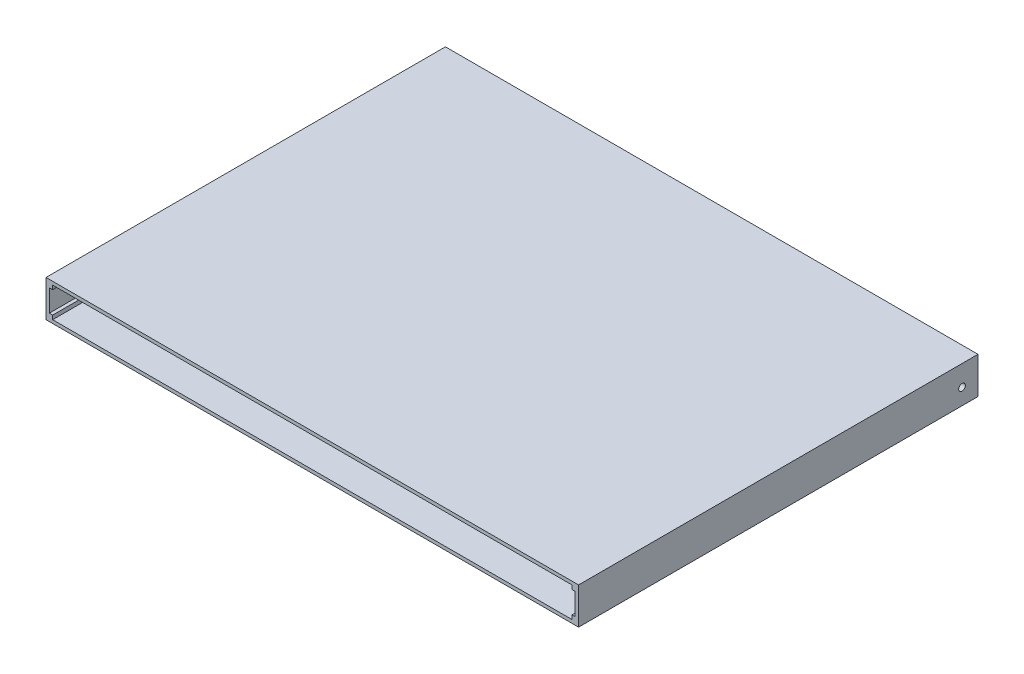
SolidWorks part; units mm, degrees
ref_plane "Front Plane" through (0, 0, 0) normal (0, 0, 1) x (1, 0, 0)
ref_plane "Top Plane" through (0, 0, 0) normal (0, 1, 0) x (1, 0, 0)
ref_plane "Right Plane" through (0, 0, 0) normal (1, 0, 0) x (0, 0, -1)
sketch "Sketch1" plane through (0, 0, 0) normal (0, 1, 0) x (1, 0, 0)
  line L1 (-254, 190.5) -> (254, 190.5)
  line L2 (-254, 190.5) -> (-254, -190.5)
  line L3 (-254, -190.5) -> (254, -190.5)
  line L4 (254, 190.5) -> (254, -190.5)
  line L5 (-254, 190.5) -> (254, -190.5) construction
  line L6 (-254, -190.5) -> (254, 190.5) construction
  point P0 (0, 0)
  dimension "D1" = 381
  dimension "D2" = 508
extrude "Boss-Extrude1" add sketch "Sketch1" along normal blind 34.925
sketch "Sketch2" plane through (0, 0, 190.5) normal (0, 0, 1) x (1, 0, 0)
  line L0 (-254, 34.925) -> (-254, 0) construction
  line L1 (250.825, 31.75) -> (-250.825, 31.75)
  line L2 (250.825, 31.75) -> (250.825, 3.175)
  line L3 (250.825, 3.175) -> (-250.825, 3.175)
  line L4 (-250.825, 31.75) -> (-250.825, 3.175)
  line L5 (250.825, 31.75) -> (-250.825, 3.175) construction
  line L6 (250.825, 3.175) -> (-250.825, 31.75) construction
  line L7 (254, 34.925) -> (254, 0) construction
  line L8 (-254, 34.925) -> (254, 34.925) construction
  line L9 (-254, 0) -> (254, 0) construction
  point P0 (0, 17.4625)
  dimension "D1" = 3.175
  dimension "D2" = 3.175
  dimension "D3" = 3.175
  dimension "D4" = 3.175
extrude "Cut-Extrude1" cut sketch "Sketch2" against normal blind 342.9
sketch "Sketch3" plane through (0, 0, 190.5) normal (0, 0, 1) x (1, 0, 0)
  line L0 (0, -55) -> (0, 55) construction
  line L1 (-250.825, 31.75) -> (-247.65, 31.75)
  line L2 (-250.825, 31.75) -> (-250.825, 27.94)
  line L3 (-250.825, 27.94) -> (-247.65, 27.94)
  line L4 (-247.65, 31.75) -> (-247.65, 27.94)
  line L5 (-250.825, 3.175) -> (-247.65, 3.175)
  line L6 (-250.825, 3.175) -> (-250.825, 6.985)
  line L7 (-250.825, 6.985) -> (-247.65, 6.985)
  line L8 (-247.65, 3.175) -> (-247.65, 6.985)
  line L9 (250.825, 6.985) -> (247.65, 6.985)
  line L10 (247.65, 3.175) -> (247.65, 6.985)
  line L11 (250.825, 3.175) -> (247.65, 3.175)
  line L12 (250.825, 3.175) -> (250.825, 6.985)
  line L13 (250.825, 27.94) -> (247.65, 27.94)
  line L14 (247.65, 31.75) -> (247.65, 27.94)
  line L15 (250.825, 31.75) -> (247.65, 31.75)
  line L16 (250.825, 31.75) -> (250.825, 27.94)
  dimension "D1" = 3.175
  dimension "D2" = 3.81
extrude "Boss-Extrude2" add sketch "Sketch3" against normal blind 35.56
sketch "Sketch4" plane through (-254, 0, 0) normal (-1, 0, 0) x (0, 0, 1)
  line L2 (-190.5, 0) -> (190.5, 0) construction
  line L3 (190.5, 34.925) -> (190.5, 0) construction
  circle A0 centre (-175.26, 15.24) radius 3.175
  dimension "D1" = 6.35
  dimension "D2" = 15.24
  dimension "D3" = 365.76
extrude "Cut-Extrude2" cut sketch "Sketch4" against normal blind 25.4
extrude "Cut-Extrude3" cut sketch "Sketch4<2>" along normal blind 25.4 from surface starting at face at (254, 17.4625, 0)
sketch "Sketch4<2>" plane through (-254, 0, 0) normal (-1, 0, 0) x (0, 0, 1) same geometry as "Sketch4"
